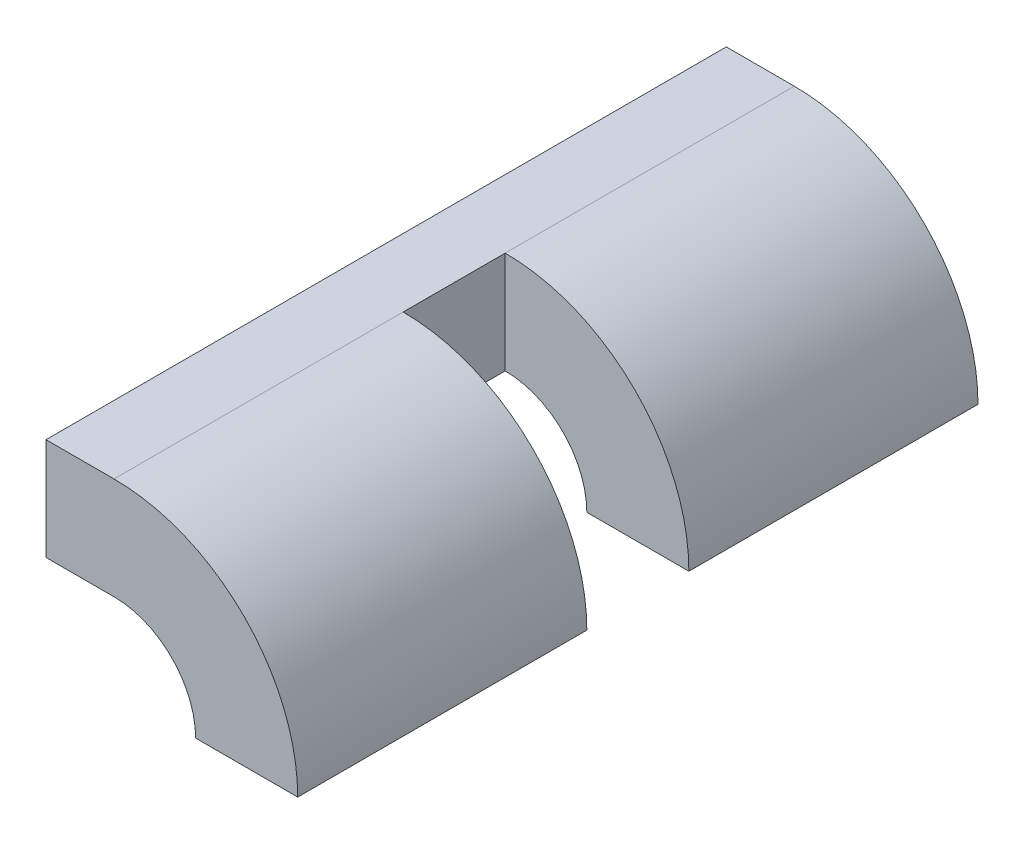
SolidWorks part; units mm, degrees
ref_plane "前视基准面" through (0, 0, 0) normal (0, 0, 1) x (1, 0, 0)
ref_plane "上视基准面" through (0, 0, 0) normal (0, 1, 0) x (1, 0, 0)
ref_plane "右视基准面" through (0, 0, 0) normal (1, 0, 0) x (0, 0, -1)
sketch "草图1" plane through (0, 0, 0) normal (0, 0, 1) x (1, 0, 0)
  line L0 (44, -24) -> (74, -24)
  line L1 (0, 0) -> (20, 0)
  line L2 (0, 0) -> (0, 30)
  line L3 (0, 30) -> (20, 30)
  line L4 (20, 0) -> (20, 30)
  arc A0 (20, 30) -> (74, -24) centre (20, -24) cw
  arc A1 (20, 0) -> (44, -24) centre (20, -24) cw
  dimension "D3" = 24
  dimension "D1" = 20
  dimension "D2" = 30
extrude "凸台-拉伸1" add sketch "草图1" along normal blind 200 contours L2 L1 L4 L3
extrude "凸台-拉伸2" add sketch "草图1<3>" along normal blind 200 contours L4 A1 L0 A0 region at (46.0524, 2.0524, 0)
sketch "草图1<3>" plane through (0, 0, 0) normal (0, 0, 1) x (1, 0, 0) same geometry as "草图1"
ref_plane "基准面1" through (74, 0, 0) normal (1, 0, 0) x (0, 0, -1)
sketch "草图2" plane through (74, 0, 0) normal (1, 0, 0) x (0, 0, -1)
  line L0 (-115, -24) -> (-115, 55.3891)
  line L1 (-200, 30) -> (-200, -24) construction
  line L2 (0, -24) -> (0, 30) construction
  line L3 (-115, 55.3891) -> (-85, 55.3891)
  line L4 (-85, 55.3891) -> (-85, -24)
  line L5 (-85, -24) -> (-115, -24)
  dimension "D1" = 85
  dimension "D2" = 85
extrude "切除-拉伸1" cut sketch "草图2" against normal blind 54 contours L5 L0 L3 L4
